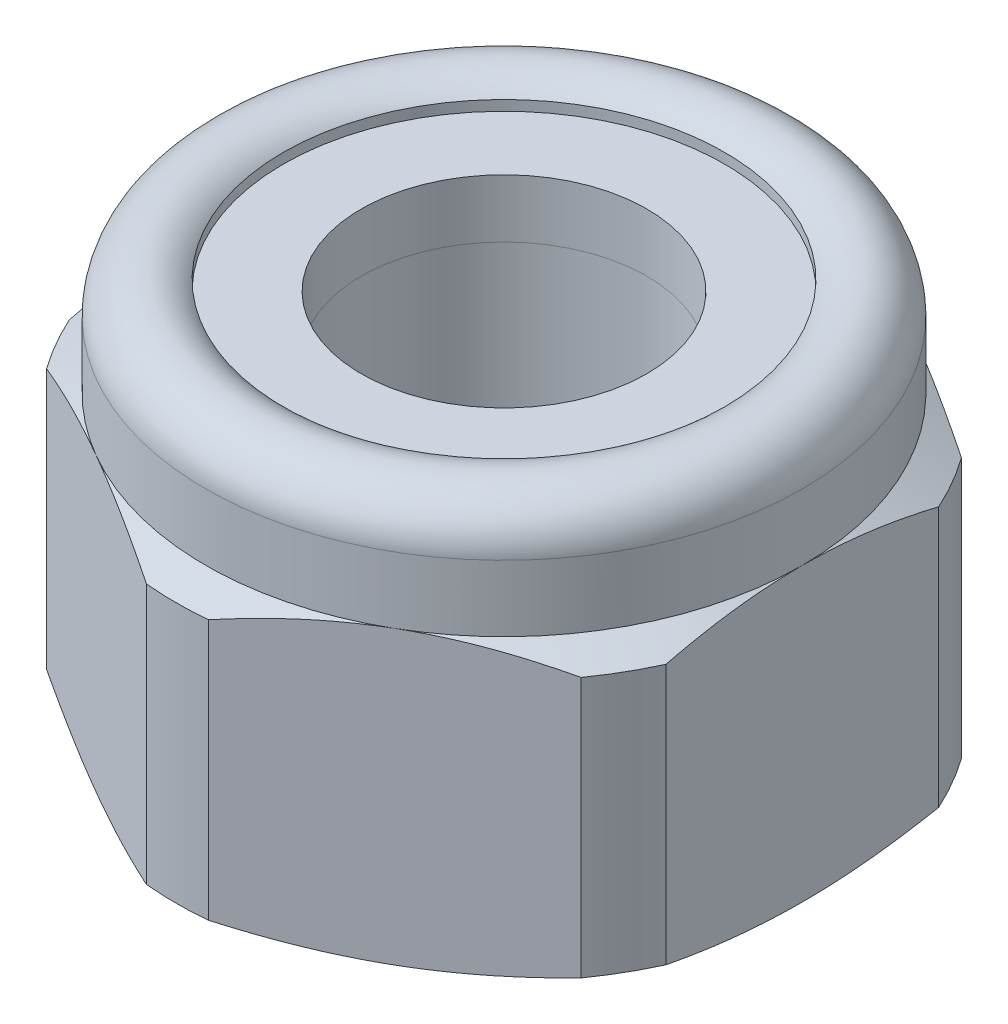
SolidWorks part; units mm, degrees
material "Alloy Steel"
ref_plane "Front Plane" through (0, 0, 0) normal (0, 0, 1) x (1, 0, 0)
ref_plane "Top Plane" through (0, 0, 0) normal (0, 1, 0) x (1, 0, 0)
ref_plane "Right Plane" through (0, 0, 0) normal (1, 0, 0) x (0, 0, -1)
sketch "Sketch1" plane through (0, 0, 0) normal (0, 0, 1) x (1, 0, 0)
  line L0 (0, -4.3688) -> (0, 4.3688) construction
  line L1 (6.3754, 0) -> (-6.3754, 0) construction
  line L2 (3.9687, -4.3688) -> (-3.9688, -4.3688) construction
  line L3 (3.9687, -4.3688) -> (3.9687, -2.9577) construction
  line L4 (-7.0104, -4.3688) -> (7.0104, -4.3688) construction
  line L5 (-7.0104, -4.3688) -> (-7.0104, 1.9812) construction
  point P4 (0, 0)
  point P8 (0, 0)
  point P11 (0, -4.3688)
  dimension "Height" = 8.7376
  dimension "Width" = 12.7508
  dimension "Thread Size" = 7.9375
  dimension "Thread Pitch" = 1.4111
  dimension "C (ref)" = 14.0208
  dimension "D (ref)" = 6.35
sketch "Sketch2" plane through (0, 0, 0) normal (0, 1, 0) x (1, 0, 0)
  line L0 (-3.9688, 0.6174) -> (-3.9688, -0.6174) construction
  line L1 (0, 7.3617) -> (-6.3754, 3.6808)
  line L2 (-6.3754, 3.6808) -> (-6.3754, -3.6808)
  line L3 (-6.3754, -3.6808) -> (0, -7.3617)
  line L4 (0, -7.3617) -> (6.3754, -3.6808)
  line L5 (6.3754, -3.6808) -> (6.3754, 3.6808)
  line L6 (6.3754, 3.6808) -> (0, 7.3617)
  line L7 (-3.9688, -0.6174) -> (-3.0522, -0.0882) construction
  line L8 (-3.0522, -0.0882) -> (-3.0522, 0.0882) construction
  line L9 (-3.0522, 0.0882) -> (-3.9688, 0.6174) construction
  line L10 (-3.0522, 0) -> (-3.9688, 0) construction
  line L11 (-3.5105, 0.3528) -> (-3.5105, -0.3528) construction
  line L12 (3.9687, 0) -> (-3.9688, 0) construction
  line L13 (6.3754, 0) -> (-6.3754, 0) construction
  circle A0 centre (0, 0) radius 6.3754 construction
  circle A1 centre (0, 0) radius 3.0522
  point P19 (0, -3.0522)
  dimension "D1" = 0.1764
  dimension "D2" = 0.7056
  dimension "D3" = 60
extrude "Boss-Extrude1" add sketch "Sketch2" along normal up to vertex (4.3688 mm away) and the other way up to vertex (4.3688 mm away) up to point (0, 4.3688, 0) other way up to point (0, -4.3688, 0)
sketch "Sketch3" plane through (0, 0, 0) normal (1, 0, 0) x (0, 0, -1)
  line L0 (7.3617, 1.9812) -> (7.3617, 5.3688)
  line L1 (4.7138, 2.6213) -> (6.3754, 2.6213) construction
  line L2 (6.1204, -4.3688) -> (7.3617, -3.79)
  line L3 (3.6808, -4.3688) -> (7.3617, -4.3688) construction
  line L4 (7.3617, 4.3688) -> (7.3617, -4.3688) construction
  line L5 (7.3617, -3.79) -> (7.3617, -4.3688)
  line L6 (7.3617, -4.3688) -> (6.1204, -4.3688)
  line L7 (6.3754, 1.9812) -> (7.3617, 1.4024)
  line L8 (7.3617, 1.4024) -> (7.3617, 1.9812)
  line L9 (6.3754, 2.6213) -> (6.3754, 1.9812) construction
  line L10 (3.6808, -4.3688) -> (7.3617, -4.3688) construction
  line L11 (6.3754, 1.9812) -> (6.3754, 3.3955)
  line L12 (3.6808, 4.3688) -> (7.3617, 4.3688) construction
  line L13 (3.0522, 2.6213) -> (4.7138, 2.6213)
  line L14 (4.7138, 2.6213) -> (4.7138, 4.0837)
  line L16 (4.7138, 4.0837) -> (5.4021, 3.3955) construction
  line L17 (5.4021, 3.3955) -> (5.4021, 4.3688) construction
  line L18 (3.0522, 2.6213) -> (3.0522, 5.3688)
  line L19 (3.0522, 5.3688) -> (7.3617, 5.3688)
  line L21 (3.0522, -4.3688) -> (3.0522, -3.575)
  line L22 (-3.6808, -4.3688) -> (3.6808, -4.3688) construction
  line L24 (3.846, -4.3688) -> (3.0522, -4.3688)
  line L25 (3.0522, -3.575) -> (3.846, -4.3688)
  line L26 (7.3617, -4.3688) -> (3.6808, -4.3688) construction
  arc A0 (6.3754, 3.3955) -> (4.7138, 4.0837) centre (5.4021, 3.3955) ccw
  point P0 (6.3754, 1.9812)
  point P1 (6.3754, 0)
  point P14 (3.0522, 0)
  point P36 (6.3754, -4.3688)
  dimension "D2" = 25
  dimension "D3" = 45
  dimension "D4" = 1
  dimension "D5" = 0.7937
  dimension "D6" = 6.9901
  dimension "D7" = 0.255
  dimension "D1" = 6.35
revolve "Cut-Revolve2" cut sketch "Sketch3" angle 360 about L0
sketch "Sketch4" plane through (0, 0, 0) normal (1, 0, 0) x (0, 0, -1)
  line L0 (-4.7138, 4.0837) -> (-4.7138, 2.6213) construction
  line L1 (-3.0522, 2.6213) -> (-4.7138, 2.6213)
  line L2 (-3.0522, 2.6213) -> (-3.0522, 3.8653)
  line L3 (-3.0522, 3.8653) -> (-4.7138, 3.8653)
  line L4 (-4.7138, 2.6213) -> (-4.7138, 3.8653)
  line L5 (4.7138, 4.0837) -> (-4.7138, 4.0837) construction
  line L6 (3.0522, 2.6213) -> (-3.0522, 2.6213) construction
  dimension "D1" = 0.2184
revolve "Revolve1" add sketch "Sketch4" angle 360 about L0
sketch "Sketch5" plane through (0, 0, 0) normal (0, 1, 0) x (1, 0, 0)
  circle A0 centre (0, 0) radius 3.0522 construction
  point P0 (0, -3.0522)
sketch "Sketch11" plane through (0, -4.3688, 0) normal (0, -1, 0) x (1, 0, 0)
  circle A0 centre (0, 0) radius 7.0104
extrude "Cut-Extrude1" cut sketch "Sketch11" against normal through all flip side to cut
sketch "Sketch6" [suppressed] plane through (0, 0, 0) normal (0, 0, 1) x (1, 0, 0)
  line L0 (3.9687, 2.6213) -> (3.9687, -4.3688)
  line L2 (0, -4.3688) -> (6.3754, -4.3688) construction
  line L3 (3.9687, -4.3688) -> (0, -4.3688)
  line L4 (0, -4.3688) -> (0, 2.6213)
  line L5 (0, -4.3688) -> (0, 4.3688) construction
  line L6 (0, 2.6213) -> (3.9687, 2.6213)
  point P1 (0, 2.6213)
revolve "Revolve2" [suppressed] add sketch "Sketch6" angle 360 about L4
sketch "Sketch7" [suppressed] plane through (0, -4.3688, 0) normal (0, -1, 0) x (1, 0, 0)
  circle A2 centre (0, 0) radius 3.9687
  circle A3 centre (0, 0) radius 3.9687
  dimension "D1" = 0
curve "Helix/Spiral1" [suppressed] pitch 1.4111 height 8.7376 turns 6.192
sketch "Sketch8" [suppressed] plane through (0, 0, 0) normal (0, 0, 1) x (1, 0, 0)
  line L0 (4.1215, -4.2806) -> (2.8994, -4.9862) construction
  line L1 (2.8994, -4.9862) -> (4.1215, -5.6917) construction
  line L2 (4.1215, -5.6917) -> (4.1215, -4.2806) construction
  line L3 (3.0522, -4.898) -> (3.0522, -5.0744)
  line L4 (3.9687, -4.3688) -> (3.9687, -5.6035) construction
  line L5 (3.9687, -4.9862) -> (4.1215, -4.9862) construction
  line L6 (2.8994, -4.9862) -> (3.0522, -4.9862) construction
  line L7 (4.0451, -4.9862) -> (4.0451, -5.6476) construction
  line L8 (3.0522, -4.898) -> (4.1215, -4.2806)
  line L9 (4.1215, -4.2806) -> (4.0451, -5.6476)
  line L10 (3.0522, -5.0744) -> (4.0451, -5.6476)
  dimension "D1" = 1.4111
  dimension "D2" = 0.1764
sweep "Cut-Sweep1" [suppressed] cut profiles "Sketch8" path "Helix/Spiral1"
sketch "Sketch9" [suppressed] plane through (0, 0, 0) normal (0, 0, 1) x (1, 0, 0)
  line L0 (0, -0.4) -> (0, -4.3688)
  line L1 (0, -0.4) -> (0, 0.3937)
  line L2 (0, -4.3688) -> (3.9687, -4.3688)
  line L3 (3.9687, -4.3688) -> (4.7625, -4.3688)
  line L4 (4.7625, -4.3688) -> (0, 0.3937)
  dimension "D1" = 0.7937
revolve "Revolve3" [suppressed] add sketch "Sketch9" angle 360 about L0
sketch "Sketch10" [suppressed] plane through (0, -4.3688, 0) normal (0, -1, 0) x (1, 0, 0)
  circle A0 centre (0, 0) radius 3.846 construction
  circle A1 centre (0, 0) radius 3.846
extrude "Boss-Extrude2" [suppressed] add sketch "Sketch10" against normal up to surface (6.9901 mm away)
combine bodies "Combine1" [suppressed] operation type add bodies to combine 110 109
equation "\"D5@Sketch3\"=\"Thread Size@Sketch1\"*.1"
equation "\"D4@Helix/Spiral1\" = \"Thread Pitch@Sketch1\""
equation "\"D3@Helix/Spiral1\" = \"Height@Sketch1\""
equation "\"D1@Sketch8\" = \"Thread Pitch@Sketch1\""
equation "\"D2@Sketch8\" = \"Thread Pitch@Sketch1\" / 8"
equation "\"D1@Sketch9\"=\"Thread Size@Sketch1\" * .1"
equation "\"D1@Sketch2\" = \"Thread Pitch@Sketch1\" / 8"
equation "\"D2@Sketch2\" = \"Thread Pitch@Sketch1\" / 2"
equation "\"D1@Sketch4\"=\"Height@Sketch1\" * .025"
equation "\"D6@Sketch3\"=\"Height@Sketch1\" *.8"
equation "\"D7@Sketch3\"=\"Width@Sketch1\"*.02"
equation "\"D1@Sketch3\" = \"D (ref)@Sketch1\""
